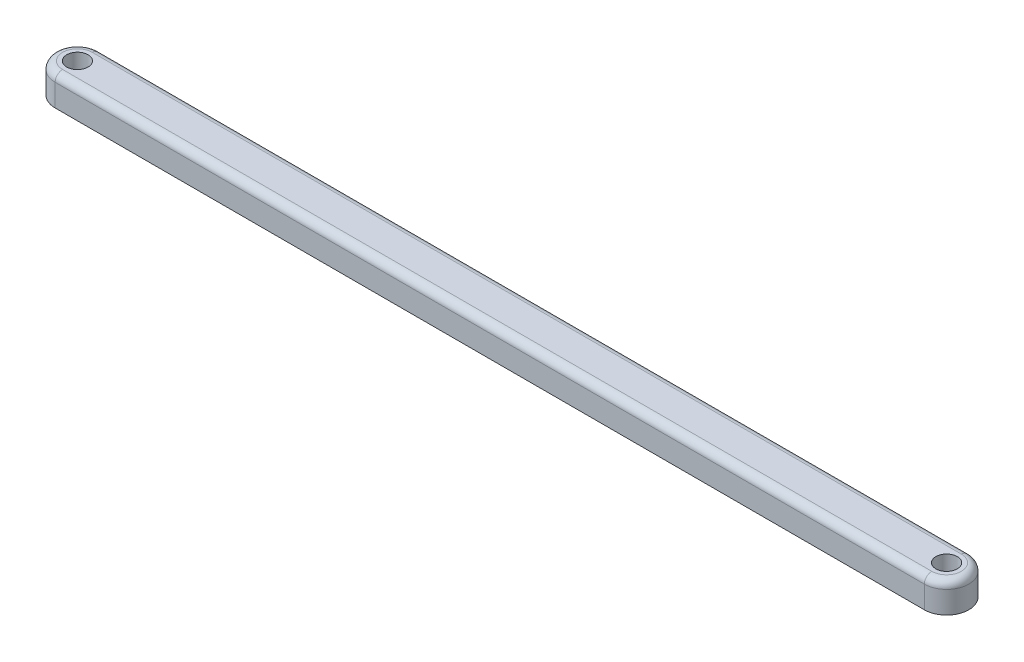
SolidWorks part; units mm, degrees
ref_plane "Front Plane" through (0, 0, 0) normal (0, 0, 1) x (1, 0, 0)
ref_plane "Top Plane" through (0, 0, 0) normal (0, 1, 0) x (1, 0, 0)
ref_plane "Right Plane" through (0, 0, 0) normal (1, 0, 0) x (0, 0, -1)
sketch "Sketch1" plane through (0, 0, 0) normal (0, 1, 0) x (1, 0, 0)
  line L0 (0, 0) -> (186.055, 0) construction
  line L1 (0, 4.7625) -> (186.055, 4.7625)
  line L2 (0, -4.7625) -> (186.055, -4.7625)
  arc A0 (0, 4.7625) -> (0, -4.7625) centre (0, 0) ccw
  arc A1 (186.055, -4.7625) -> (186.055, 4.7625) centre (186.055, 0) ccw
  point P3 (93.0275, 0)
  dimension "D1" = 186.055
  dimension "D2" = 9.525
extrude "Boss-Extrude1" add sketch "Sketch1" along normal mid plane 6.35
sketch "Sketch2" plane through (0, 3.175, 0) normal (0, 1, 0) x (1, 0, 0)
  circle A0 centre (0, 0) radius 2.286
  circle A1 centre (186.055, 0) radius 2.286
  dimension "D1" = 4.572
extrude "Cut-Extrude1" cut sketch "Sketch2" against normal through all
fillet "Fillet1" radius 1.5875 4 edges at (190.8175, 3.175, 0) (93.0275, 3.175, 4.7625) (-4.7625, 3.175, 0) (93.0275, 3.175, -4.7625)
